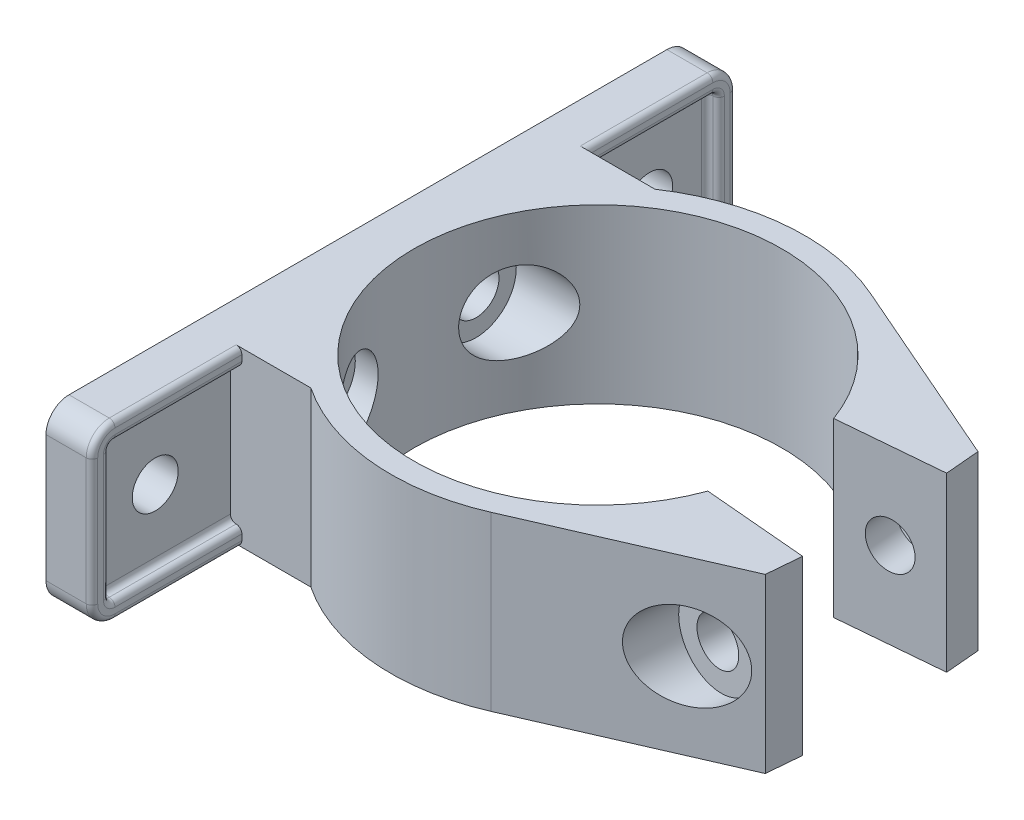
SolidWorks part; units mm, degrees
ref_plane "Front Plane" through (0, 0, 0) normal (0, 0, 1) x (1, 0, 0)
ref_plane "Top Plane" through (0, 0, 0) normal (0, 1, 0) x (1, 0, 0)
ref_plane "Right Plane" through (0, 0, 0) normal (1, 0, 0) x (0, 0, -1)
sketch "Sketch1" plane through (0, 0, 0) normal (0, 1, 0) x (1, 0, 0)
  line L0 (-16, 14.9666) -> (-16, 28)
  line L1 (-16, 28) -> (-20, 28)
  line L2 (-20, 28) -> (-20, -28)
  line L3 (-20, -28) -> (-16, -28)
  line L4 (-16, -28) -> (-16, -14.9666)
  line L5 (15.8376, 8.554) -> (23.8071, 9.2512)
  line L6 (23.8071, 9.2512) -> (24.0686, 6.2627)
  line L7 (24.0686, 6.2627) -> (15.0351, 5.4723)
  line L8 (15.0351, -5.4723) -> (24.0686, -6.2627)
  line L9 (24.0686, -6.2627) -> (23.8071, -9.2512)
  line L10 (23.8071, -9.2512) -> (15.8376, -8.554)
  line L11 (23.1185, 0) -> (108.7292, 0) construction
  line L12 (-10, 14.9666) -> (-16, 14.9666)
  line L13 (-16, -14.9666) -> (-10, -14.9666)
  line L14 (0, 0) -> (15.0351, -5.4723) construction
  arc A0 (15.0351, 5.4723) -> (15.0351, -5.4723) centre (0, 0) ccw
  arc A1 (-10, -14.9666) -> (15.8376, -8.554) centre (0, 0) ccw
  arc A2 (15.8376, 8.554) -> (-10, 14.9666) centre (0, 0) ccw
  dimension "D1" = 2
  dimension "D2" = 32
  dimension "D3" = 8
  dimension "D4" = 28
  dimension "D5" = 4
  dimension "D6" = 20
  dimension "D7" = 3
  dimension "D8" = 6
  dimension "D9" = 20
  dimension "D10" = 10
extrude "Boss-Extrude1" add sketch "Sketch1" along normal blind 7.5 and the other way blind 7.5
hole_wizard "Ø4.0 (4) Diameter Hole1" positions "Sketch5" profile "Sketch4" hole size "Ø4.0" standard "Ansi Metric" end condition through all
sketch "Sketch5" plane through (-16, 0, 0) normal (1, 0, 0) x (0, 0, -1)
  line L1 (-28, -7.5) -> (-28, 7.5) construction
  line L2 (0, 55) -> (0, -55) construction
  line L3 (0, 6.5274) -> (0, -9.5783) construction
  line L5 (55, 0) -> (-55, 0) construction
  point P1 (-21.5, 0)
  point P3 (21.5, 0)
  point P23 (-7, 0)
  point P25 (7, 0)
  dimension "D1" = 6.5
  dimension "D2" = 7
sketch "Sketch4" plane through (-16, 0, 21.5) normal (0, 1, 0) x (0, 0, -1)
  line L0 (0, 0) -> (0, 4)
  line L1 (0, 4) -> (2, 4)
  line L2 (2, 4) -> (2, 0)
  line L5 (2, 0) -> (0, 0)
  line L11 (0, -6.35) -> (0, 107.95) construction
  dimension "Thru Hole Dia." = 4
  dimension "Thru Hole Depth" = 4
fillet "Fillet1" radius 2 4 edges at (-18, -7.5, -28) (-18, 7.5, -28) (-18, -7.5, 28) (-18, 7.5, 28)
sketch "Sketch10" plane through (-16, 0, 0) normal (1, 0, 0) x (0, 0, -1)
  line L0 (-14.9666, -7.5) -> (-14.9666, 7.5) construction
  line L1 (14.9666, -7.5) -> (14.9666, 7.5) construction
  line L2 (14.9666, 6) -> (14.9666, -6)
  line L3 (-14.9666, 6) -> (-14.9666, -6)
  line L102 (-26.5, 5.5) -> (-26.5, -5.5)
  line L103 (-26, -6) -> (-16.4666, -6)
  line L104 (-16.4666, -6) -> (-16.4666, 6)
  line L105 (-16.4666, 6) -> (-26, 6)
  line L106 (-26.5, 5.5) -> (-26.5, -5.5)
  line L107 (-26, -6) -> (-14.9666, -6)
  line L109 (-14.9666, 6) -> (-26, 6)
  line L114 (16.4666, -6) -> (26, -6)
  line L115 (26.5, -5.5) -> (26.5, 5.5)
  line L116 (26, 6) -> (16.4666, 6)
  line L117 (16.4666, 6) -> (16.4666, -6)
  line L118 (14.9666, -6) -> (26, -6)
  line L119 (26.5, -5.5) -> (26.5, 5.5)
  line L120 (26, 6) -> (14.9666, 6)
  arc A52 (-26.5, -5.5) -> (-26, -6) centre (-26, -5.5) ccw
  arc A53 (-26, 6) -> (-26.5, 5.5) centre (-26, 5.5) ccw
  arc A54 (-26.5, -5.5) -> (-26, -6) centre (-26, -5.5) ccw
  arc A55 (-26, 6) -> (-26.5, 5.5) centre (-26, 5.5) ccw
  arc A58 (26, -6) -> (26.5, -5.5) centre (26, -5.5) ccw
  arc A59 (26.5, 5.5) -> (26, 6) centre (26, 5.5) ccw
  arc A60 (26, -6) -> (26.5, -5.5) centre (26, -5.5) ccw
  arc A61 (26.5, 5.5) -> (26, 6) centre (26, 5.5) ccw
  dimension "D1" = 1.5
  dimension "D2" = 1.5
extrude "Cut-Extrude1" cut sketch "Sketch10" against normal blind 1
sketch "Sketch15" plane through (-17, 0, 0) normal (1, 0, 0) x (0, 0, -1)
  circle A0 centre (7, 0) radius 3.5
  circle A1 centre (-7, 0) radius 3.5
  dimension "D1" = 7
extrude "Cut-Extrude5" cut sketch "Sketch15" along normal up to next and the other way blind 0.6
fillet "Fillet2" radius 0.5 30 edges at (-17, -6, -20.4833) (-17, -5.8536, -26.3536) (-17, 0, -26.5) (-17, 5.8536, -26.3536) (-16, -6, -20.4833) (-16, -5.8536, -26.3536) (-16, 6, -20.4833) (-16, 5.8536, -26.3536) (-16, -7.5, -20.4833) (-16, -6.9142, -27.4142) (-16, 7.5, -20.4833) (-16, 6.9142, -27.4142) (-16, -7.5, 20.4833) (-16, -6.9142, 27.4142) (-16, 0, 28) (-16, 6.9142, 27.4142) (-17, -6, 20.4833) (-17, -5.8536, 26.3536) (-17, 0, 26.5) (-17, 5.8536, 26.3536) (-16, -6, 20.4833) (-16, -5.8536, 26.3536) (-16, 0, 26.5) (-16, 5.8536, 26.3536) (-17, 6, -20.4833) (-16, 0, -26.5) (-16, 0, -28) (-16, 7.5, 20.4833) (-17, 6, 20.4833) (-16, 6, 20.4833)
sketch "Sketch11" plane through (0, 0, 0) normal (0, 1, 0) x (1, 0, 0)
  line L1 (15.8376, -8.554) -> (23.8071, -9.2512) construction
  line L2 (23.8071, -9.2512) -> (7.1984, -16.498)
  line L4 (23.8071, -9.2512) -> (15.8376, -8.554)
  line L6 (23.8071, 9.2512) -> (15.8376, 8.554) construction
  line L7 (23.8071, 9.2512) -> (7.1984, 16.498)
  line L8 (23.8071, 9.2512) -> (15.8376, 8.554)
  arc A0 (-10, -14.9666) -> (15.8376, -8.554) centre (0, 0) ccw construction
  arc A3 (15.8376, 8.554) -> (7.1984, 16.498) centre (0, 0) ccw
  arc A4 (15.0351, 5.4723) -> (15.0351, -5.4723) centre (0, 0) ccw construction
  arc A5 (15.8376, 8.554) -> (-10, 14.9666) centre (0, 0) ccw construction
  arc A6 (7.1984, -16.498) -> (15.8376, -8.554) centre (0, 0) ccw
extrude "Boss-Extrude2" add sketch "Sketch11" against normal up to surface (7.5 mm away) and the other way up to surface (7.5 mm away) up to face at (0.206, -7.5, 0) other way up to face at (0.206, 7.5, 0)
sketch "Sketch16" plane through (0, 0, 0) normal (0, 1, 0) x (1, 0, 0)
  line L0 (19.5518, -5.8675) -> (18.9072, -13.2359) construction
  line L1 (24.0686, -6.2627) -> (15.0351, -5.4723) construction
  line L2 (19.5518, -5.8675) -> (21.5442, -6.0418)
  line L3 (21.5442, -6.0418) -> (21.2828, -9.0304)
  line L4 (21.2828, -9.0304) -> (23.0261, -9.1829)
  line L5 (23.0261, -9.1829) -> (22.0797, -20.0005)
  line L6 (22.0797, -20.0005) -> (18.344, -19.6736)
  line L7 (18.344, -19.6736) -> (19.5518, -5.8675)
  line L8 (23.8071, -9.2512) -> (24.0686, -6.2627) construction
  arc A0 (-10, -14.9666) -> (7.1984, -16.498) centre (0, 0) ccw construction
  dimension "D1" = 2
  dimension "D2" = 3.75
revolve "Cut-Revolve1" cut sketch "Sketch16" angle 360 about L0
ref_plane "Left Oblique Plane" through (-0.6224, 0, -7.1139) normal (0.0872, 0, 0.9962) x (0.9962, 0, -0.0872)
sketch "Sketch17" plane through (-0.6224, 0, -7.1139) normal (0.0872, 0, 0.9962) x (0.9962, 0, -0.0872)
  line L0 (55, 0) -> (-55, 0) construction
  line L1 (15.4548, 7.5) -> (24.5229, 7.5) construction
  circle A0 centre (19.9888, 0) radius 2
  point P4 (19.9888, 7.5)
  dimension "D1" = 4
extrude "Cut-Extrude6" cut sketch "Sketch17" along normal up to next
sketch "Sketch18" plane through (-0.6224, 0, -7.1139) normal (0.0872, 0, 0.9962) x (0.9962, 0, -0.0872)
  line L0 (24.5229, -7.5) -> (24.5229, 7.5) construction
  line L1 (16.9888, -1.7321) -> (19.9888, -3.4641)
  line L2 (19.9888, -3.4641) -> (22.9888, -1.7321)
  line L3 (22.9888, -1.7321) -> (22.9888, 1.7321)
  line L4 (22.9888, 1.7321) -> (19.9888, 3.4641)
  line L5 (19.9888, 3.4641) -> (16.9888, 1.7321)
  line L6 (16.9888, 1.7321) -> (16.9888, -1.7321)
  circle A0 centre (19.9888, 0) radius 3 construction
  circle A1 centre (19.9888, 0) radius 2 construction
  dimension "D1" = 6
extrude "Cut-Extrude7" cut sketch "Sketch18" against normal up to next
ref_plane "Right Oblique Plane" through (-0.6224, 0, 7.1139) normal (0.0872, 0, -0.9962) x (-0.9962, 0, -0.0872)
